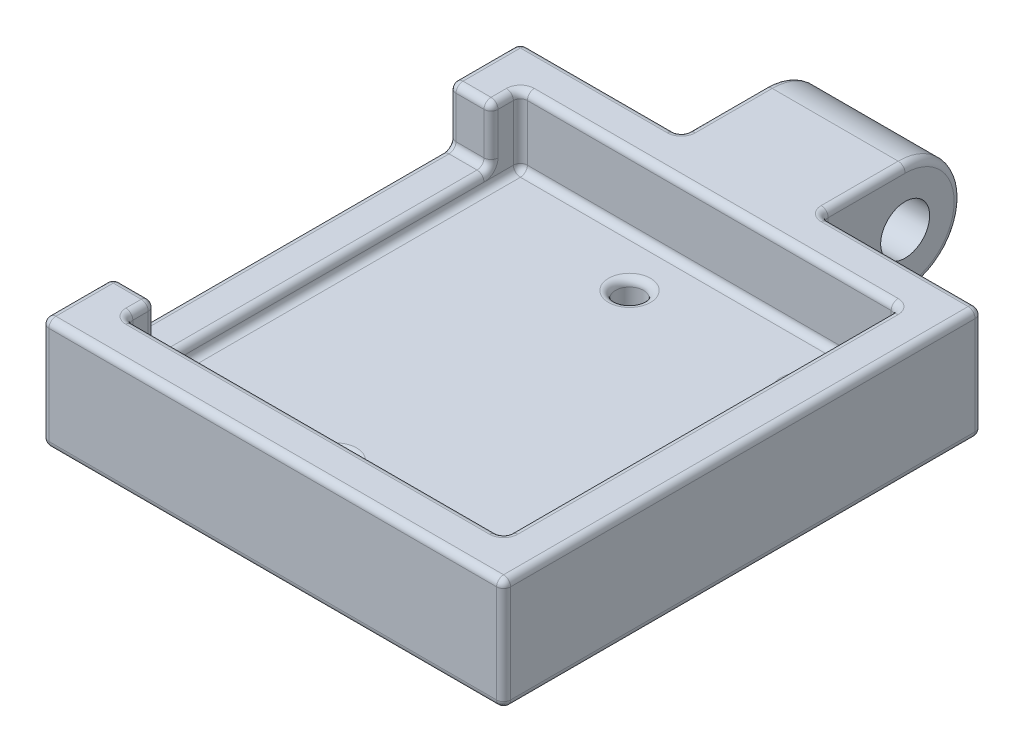
SolidWorks part; units mm, degrees
ref_plane "Front Plane" through (0, 0, 0) normal (0, 0, 1) x (1, 0, 0)
ref_plane "Top Plane" through (0, 0, 0) normal (0, 1, 0) x (1, 0, 0)
ref_plane "Right Plane" through (0, 0, 0) normal (1, 0, 0) x (0, 0, -1)
sketch "Sketch1" plane through (0, 0, 0) normal (0, 1, 0) x (1, 0, 0)
  line L0 (-16.5, -17.1) -> (-16.5, 17.1)
  line L1 (-13.5, -14.1) -> (13.5, -14.1)
  line L2 (-13.5, -14.1) -> (-13.5, 14.1)
  line L3 (-13.5, 14.1) -> (13.5, 14.1)
  line L4 (13.5, -14.1) -> (13.5, 14.1)
  line L5 (-13.5, -14.1) -> (13.5, 14.1) construction
  line L6 (-13.5, 14.1) -> (13.5, -14.1) construction
  line L7 (-16.5, 17.1) -> (16.5, 17.1)
  line L8 (16.5, -17.1) -> (16.5, 17.1)
  line L9 (-16.5, -17.1) -> (16.5, -17.1)
  point P0 (0, 0)
  dimension "D2" = 27
  dimension "D3" = 28.2
  dimension "D1" = 3
extrude "Boss-Extrude1" add sketch "Sketch1" along normal blind 5
sketch "Sketch2" plane through (0, 0, 0) normal (0, -1, 0) x (1, 0, 0)
  line L0 (16.5, -17.1) -> (-16.5, -17.1) construction
  line L1 (16.5, 17.1) -> (16.5, -17.1) construction
  line L2 (-16.5, 17.1) -> (16.5, 17.1) construction
  line L3 (-16.5, -17.1) -> (-16.5, 17.1) construction
  line L4 (16.5, -17.1) -> (-16.5, -17.1)
  line L5 (16.5, 17.1) -> (16.5, -17.1)
  line L6 (-16.5, 17.1) -> (16.5, 17.1)
  line L7 (-16.5, -17.1) -> (-16.5, 17.1)
extrude "Boss-Extrude2" add sketch "Sketch2" along normal blind 3
sketch "Sketch3" plane through (0, 0, 0) normal (0, 1, 0) x (1, 0, 0)
  line L0 (13.5, 14.1) -> (-13.5, 14.1) construction
  line L1 (-2.1, -10.5) -> (10.2, -10.5) construction
  line L2 (-2.1, -10.5) -> (-2.1, 10.5) construction
  line L3 (-2.1, 10.5) -> (10.2, 10.5) construction
  line L4 (10.2, -10.5) -> (10.2, 10.5) construction
  line L5 (-2.1, -10.5) -> (10.2, 10.5) construction
  line L6 (-2.1, 10.5) -> (10.2, -10.5) construction
  circle A0 centre (-2.1, 10.5) radius 1
  circle A1 centre (10.2, 10.5) radius 1
  circle A2 centre (10.2, -10.5) radius 1
  circle A3 centre (-2.1, -10.5) radius 1
  point P0 (4.05, 0)
  point P14 (0, 14.1)
  dimension "D1" = 2
  dimension "D2" = 12.3
  dimension "D3" = 2.1
  dimension "D4" = 21
extrude "Cut-Extrude1" cut sketch "Sketch3" against normal through all
sketch "Sketch4" plane through (0, 5, 0) normal (0, 1, 0) x (1, 0, 0)
  line L0 (-13.5, 14.1) -> (-13.5, -14.1) construction
  line L1 (-13.5, 12) -> (-16.5, 12)
  line L2 (-13.5, 12) -> (-13.5, -12)
  line L3 (-13.5, -12) -> (-16.5, -12)
  line L4 (-16.5, 12) -> (-16.5, -12)
  line L5 (-16.5, 17.1) -> (-16.5, -17.1) construction
  point P8 (-13.5, 0)
  dimension "D1" = 24
extrude "Cut-Extrude2" cut sketch "Sketch4" against normal offset from surface (4 mm away) 1 up to face at (-2.1, 0, 11.5)
sketch "Sketch5" plane through (0, 0, 0) normal (1, 0, 0) x (0, 0, -1)
  line L0 (17.1, 5) -> (23.1, 5)
  line L1 (17.1, -3) -> (23.1, -3)
  line L2 (17.1, 5) -> (17.1, -3)
  arc A0 (23.1, 5) -> (23.1, -3) centre (23.1, 1) cw
  circle A1 centre (23.1, 1) radius 1.75
  dimension "D2" = 3.5
  dimension "D1" = 6
extrude "Boss-Extrude3" add sketch "Sketch5" along normal mid plane 10
fillet "Fillet1" radius 0.5 54 edges at (10.75, 5, -17.1) (13.5, 0, 0) (13.5, 2.5, 14.1) (0, 0, -14.1) (13.5, 2.5, -14.1) (-13.5, 0, 0) (-13.5, 2.5, -14.1) (0, 0, 14.1) (-13.5, 2.5, 14.1) (13.5, 5, 0) (-16.5, 5, -14.55) (0, 5, -14.1) (-13.5, 5, -13.05) (0, 5, 14.1) (16.5, -3, 0) (0, -3, 17.1) (-16.5, -3, 0) (-10.75, -3, -17.1) (0, 5, 17.1) (-2.1, -3, 11.5) (-2.1, 0, 11.5) (10.2, -3, 11.5) (10.2, 0, 11.5) (10.2, -3, -9.5) (10.2, 0, -9.5) (-2.1, -3, -9.5) (-2.1, 0, -9.5) (-13.5, 5, 13.05) (-16.5, 5, 14.55) (-13.5, 3, -12) (-13.5, 3, 12) (-16.5, 3, 12) (-16.5, 3, -12) (-15, 5, -12) (-15, 5, 12) (-13.5, 1, 0) (-15, 1, 12) (-16.5, 1, 0) (-15, 1, -12) (-16.5, 1, 17.1) (10.75, -3, -17.1) (-16.5, 1, -17.1) (-10.75, 5, -17.1) (16.5, 1, -17.1) (5, 1, -17.1) (16.5, 1, 17.1) (5, -3, -20.1) (5, 1, -27.1) (5, 5, -20.1) (-5, 1, -17.1) (-5, -3, -20.1) (-5, 1, -27.1) (-5, 5, -20.1) (16.5, 5, 0)
